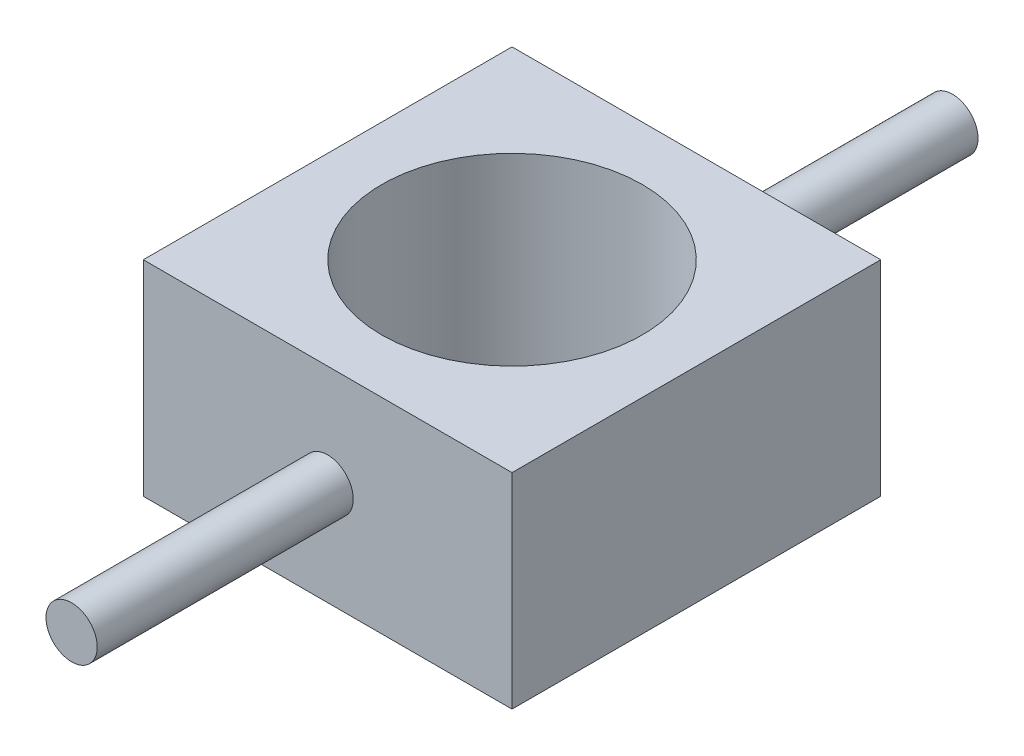
SolidWorks part; units mm, degrees
ref_plane "Front Plane" through (0, 0, 0) normal (0, 0, 1) x (1, 0, 0)
ref_plane "Top Plane" through (0, 0, 0) normal (0, 1, 0) x (1, 0, 0)
ref_plane "Right Plane" through (0, 0, 0) normal (1, 0, 0) x (0, 0, -1)
sketch "Sketch1" plane through (0, 0, 0) normal (0, 1, 0) x (1, 0, 0)
  line L1 (-18, 18) -> (18, 18)
  line L2 (-18, 18) -> (-18, -18)
  line L3 (-18, -18) -> (18, -18)
  line L4 (18, 18) -> (18, -18)
  line L5 (-18, 18) -> (18, -18) construction
  line L6 (-18, -18) -> (18, 18) construction
  point P0 (0, 0)
  dimension "D1" = 36
  dimension "D2" = 36
extrude "Boss-Extrude1" add sketch "Sketch1" along normal blind 10 and the other way blind 10
sketch "Sketch2" plane through (0, -10, 0) normal (0, -1, 0) x (1, 0, 0)
  circle A0 centre (0, 0) radius 12.725
  dimension "D1" = 25.45
extrude "Cut-Extrude1" cut sketch "Sketch2" against normal through all
sketch "Sketch5" plane through (0, 0, -18) normal (0, 0, -1) x (-1, 0, 0)
  circle A0 centre (0, 0) radius 2.5
  dimension "D1" = 5
extrude "Boss-Extrude2" add sketch "Sketch5" along normal blind 25
mirror "Mirror1" about plane through (0, 0, 0) normal (0, 0, 1) of "Boss-Extrude2"
